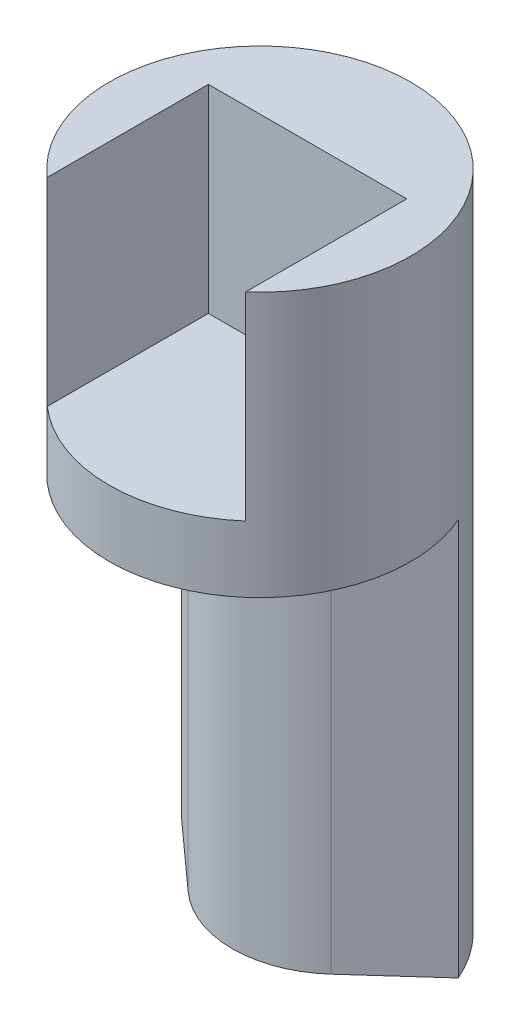
SolidWorks part; units mm, degrees
ref_plane "Front Plane" through (0, 0, 0) normal (0, 0, 1) x (1, 0, 0)
ref_plane "Top Plane" through (0, 0, 0) normal (0, 1, 0) x (1, 0, 0)
ref_plane "Right Plane" through (0, 0, 0) normal (1, 0, 0) x (0, 0, -1)
sketch "Sketch2" plane through (0, 0, 0) normal (0, 1, 0) x (1, 0, 0)
  line L0 (-6.985, 0) -> (6.985, 0) construction
  line L10 (0, 6.985) -> (0, -6.985) construction
  line L13 (0, -6.985) -> (0, 0) construction
  line L14 (-13.081, 3.175) -> (13.081, 3.175) construction
  line L15 (0, -4.445) -> (0, 3.175) construction
  line L16 (-13.081, 3.175) -> (-8.0591, -1.3498)
  line L17 (13.081, 3.175) -> (8.0591, -1.3498)
  line L18 (-11.8908, 4.4959) -> (-6.8689, -0.0289)
  line L19 (11.8908, 4.4959) -> (6.8689, -0.0289)
  line L21 (-12.4859, 3.8355) -> (12.4859, 3.8355) construction
  circle A0 centre (0, 0) radius 14.478
  arc A9 (-8.0591, -1.3498) -> (8.0591, -1.3498) centre (0, 7.5946) ccw
  arc A10 (-13.081, 3.175) -> (-11.8908, 4.4959) centre (-12.4859, 3.8355) cw
  arc A11 (-6.8689, -0.0289) -> (6.8689, -0.0289) centre (0, 7.5946) ccw
  arc A12 (11.8908, 4.4959) -> (13.081, 3.175) centre (12.4859, 3.8355) cw
  point P13 (10.1453, 10.3289)
  point P36 (0, 3.175)
  point P37 (-33.8663, 15.7634)
  point P42 (0, -4.445)
  point P47 (0, 3.175)
  dimension "D1" = 28.956
  dimension "D4" = 24.9718
  dimension "D9" = 12.0396
  dimension "D11" = 0.889
  dimension "D12" = 10.2616
  dimension "D3" = 3.175
  dimension "D10" = 6.7597
extrude "Boss-Extrude1" add sketch "Sketch2" along normal blind 50.8
sketch "Sketch15" plane through (0, 0, 0) normal (0, -1, 0) x (1, 0, 0)
  line L1 (11.8908, -4.4959) -> (13.2859, -5.7529)
  line L2 (11.8908, -4.4959) -> (6.8689, 0.0289) construction
  line L3 (-11.8908, -4.4959) -> (-13.2859, -5.7529)
  line L4 (-6.8689, 0.0289) -> (-11.8908, -4.4959) construction
  circle A0 centre (0, 0) radius 14.478 construction
  circle A1 centre (0, 0) radius 14.478
  arc A2 (13.2859, -5.7529) -> (-13.2859, -5.7529) centre (0, 0) ccw
  arc A8 (13.2859, -5.7529) -> (-13.2859, -5.7529) centre (0, 0) ccw
  circle M2 centre (0, 0) radius 14.478
  arc M3 (-11.8908, -4.4959) -> (-13.081, -3.175) centre (-12.4859, -3.8355) cw
  line M4 (-13.081, -3.175) -> (-8.0591, 1.3498)
  arc M5 (-8.0591, 1.3498) -> (8.0591, 1.3498) centre (0, -7.5946) cw
  line M6 (8.0591, 1.3498) -> (13.081, -3.175)
  arc M7 (13.081, -3.175) -> (11.8908, -4.4959) centre (12.4859, -3.8355) cw
  dimension "D1" = 0
extrude "Cut-Extrude3" cut sketch "Sketch15" against normal blind 38.1 contours M7 M2 M3 M4 M5 M6 region at (0, 0, 6.379)
sketch "Sketch16" plane through (0, 50.8, 0) normal (0, 1, 0) x (1, 0, 0)
  circle A0 centre (0, 0) radius 14.478
extrude "Boss-Extrude2" add sketch "Sketch16" against normal blind 12.7 and the other way blind 12.7
sketch "Sketch17" plane through (0, 63.5, 0) normal (0, 1, 0) x (1, 0, 0)
  line L0 (0, 4.572) -> (0, -14.478) construction
  line L1 (-9.525, -14.478) -> (9.525, -14.478)
  line L2 (-9.525, -14.478) -> (-9.525, 4.572)
  line L3 (-9.525, 4.572) -> (9.525, 4.572)
  line L4 (9.525, -14.478) -> (9.525, 4.572)
  line L5 (-9.525, -4.953) -> (9.525, -4.953) construction
  circle A0 centre (0, 0) radius 14.478 construction
  point P0 (0, 0)
  dimension "D1" = 19.05
  dimension "D2" = 19.05
extrude "Cut-Extrude4" cut sketch "Sketch17" against normal blind 19.05
